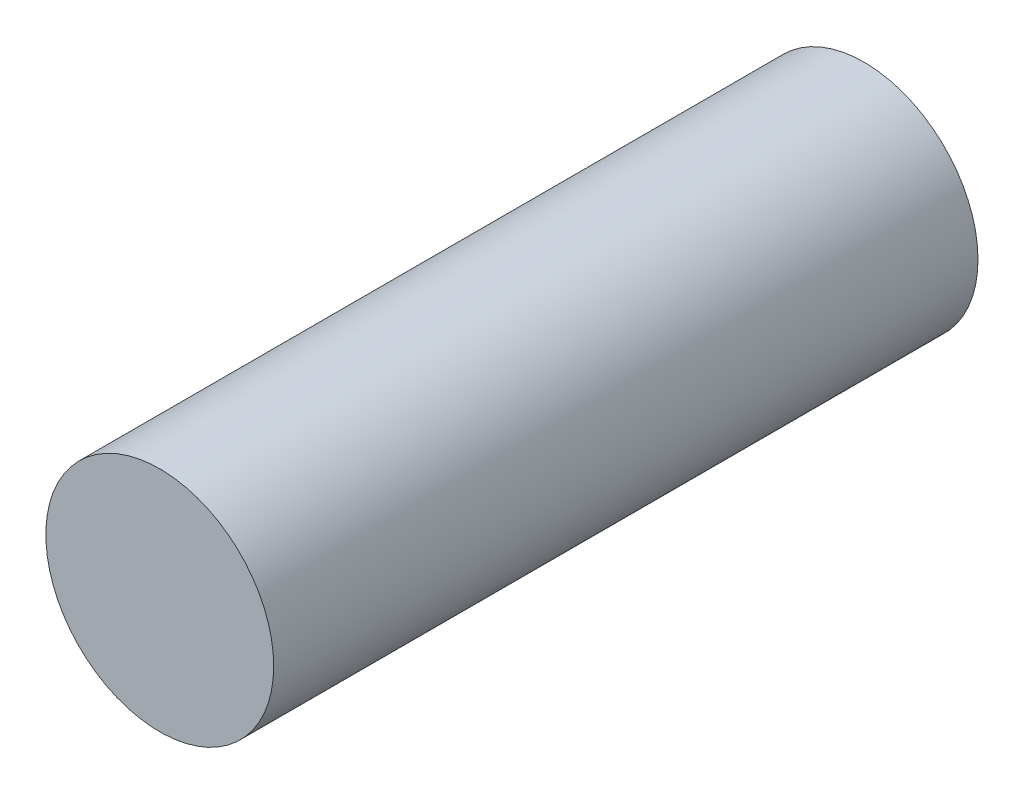
SolidWorks part; units mm, degrees
ref_plane "Front Plane" through (0, 0, 0) normal (0, 0, 1) x (1, 0, 0)
ref_plane "Top Plane" through (0, 0, 0) normal (0, 1, 0) x (1, 0, 0)
ref_plane "Right Plane" through (0, 0, 0) normal (1, 0, 0) x (0, 0, -1)
sketch "Sketch1" plane through (0, 0, 0) normal (0, 0, 1) x (1, 0, 0)
  circle A0 centre (0, 0) radius 11
  dimension "D1" = 22
extrude "Boss-Extrude1" add sketch "Sketch1" along normal blind 68
sketch "Sketch2" plane through (0, 0, 68) normal (0, 0, 1) x (1, 0, 0)
  point P0 (0, 0)
